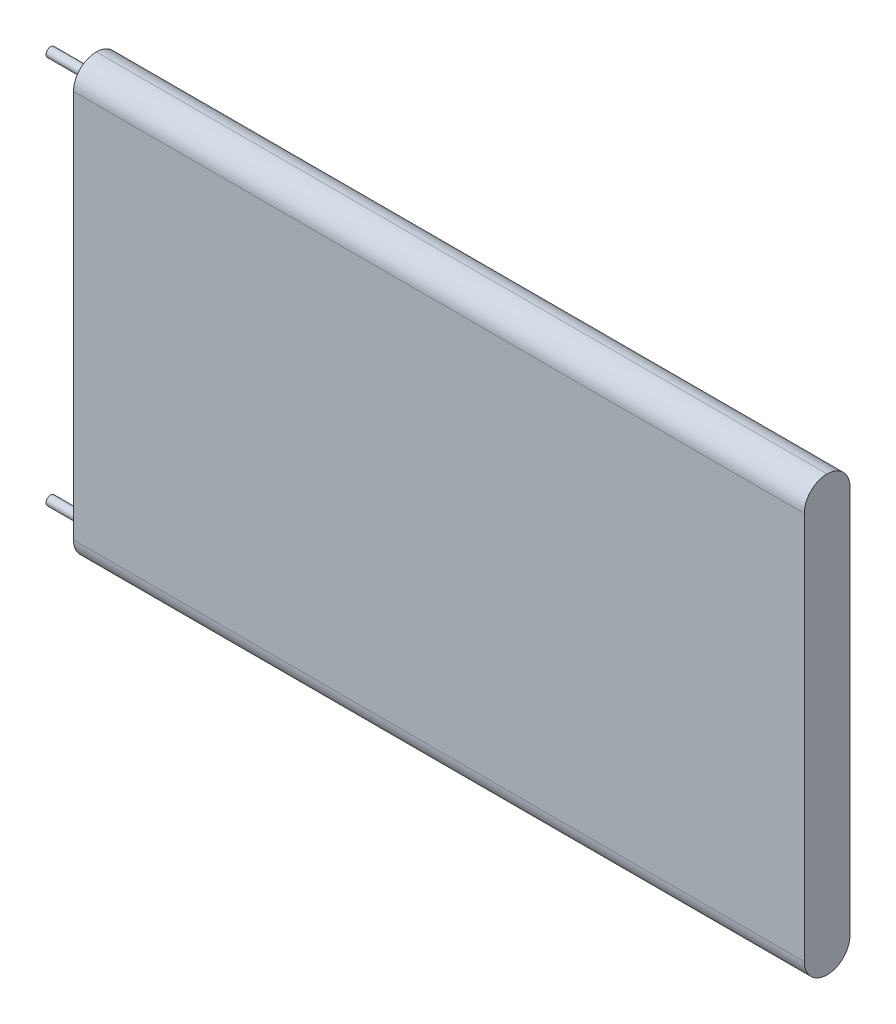
SolidWorks part; units mm, degrees
ref_plane "Front Plane" through (0, 0, 0) normal (0, 0, 1) x (1, 0, 0)
ref_plane "Top Plane" through (0, 0, 0) normal (0, 1, 0) x (1, 0, 0)
ref_plane "Right Plane" through (0, 0, 0) normal (1, 0, 0) x (0, 0, -1)
sketch "Sketch1" plane through (0, 0, 0) normal (0, 0, 1) x (1, 0, 0)
  line L1 (-50.8, -30.1625) -> (50.8, -30.1625)
  line L2 (-50.8, -30.1625) -> (-50.8, 30.1625)
  line L3 (-50.8, 30.1625) -> (50.8, 30.1625)
  line L4 (50.8, -30.1625) -> (50.8, 30.1625)
  line L5 (-50.8, -30.1625) -> (50.8, 30.1625) construction
  line L6 (-50.8, 30.1625) -> (50.8, -30.1625) construction
  point P0 (0, 0)
  dimension "D1" = 101.6
  dimension "D2" = 60.325
extrude "Boss-Extrude1" add sketch "Sketch1" along normal blind 6.35
fillet "Fillet1" radius 3.175 4 edges at (0, 30.1625, 6.35) (0, 30.1625, 0) (0, -30.1625, 6.35) (0, -30.1625, 0)
sketch "Sketch2" plane through (-50.8, 0, 0) normal (-1, 0, 0) x (0, 0, 1)
  circle A0 centre (3.175, 26.9875) radius 0.635
  circle A1 centre (3.175, -26.9875) radius 0.635
  dimension "D1" = 1.27
extrude "Boss-Extrude2" add sketch "Sketch2" along normal blind 6.35
